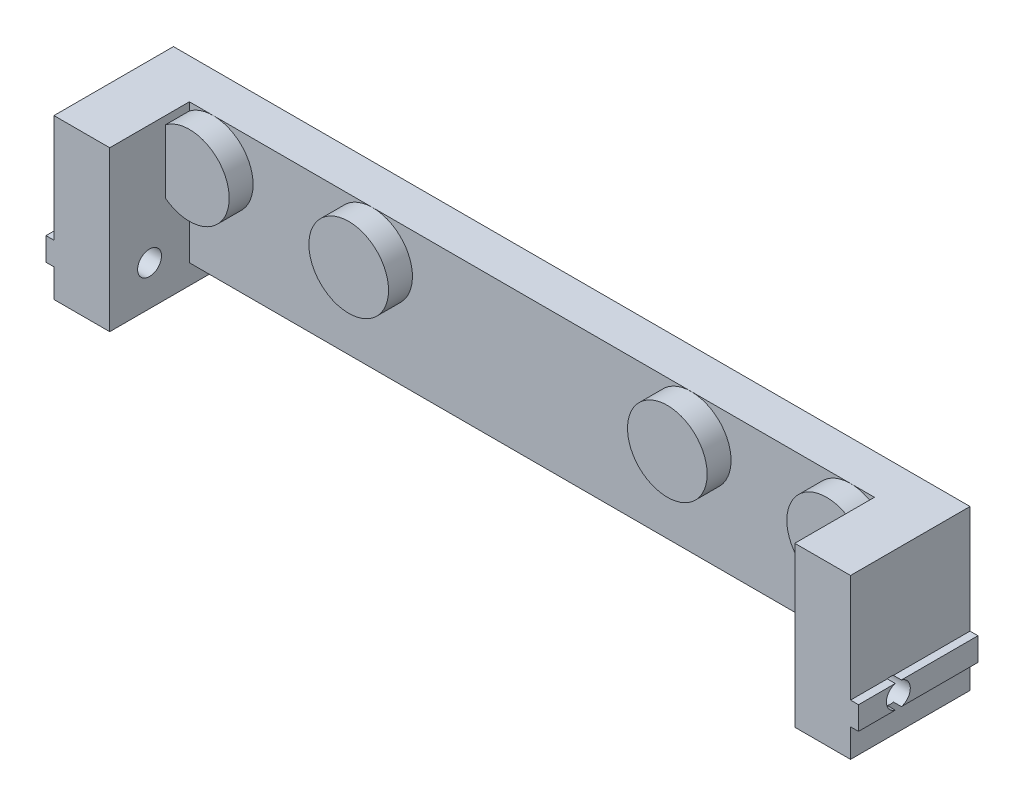
SolidWorks part; units mm, degrees
ref_plane "Front Plane" through (0, 0, 0) normal (0, 0, 1) x (1, 0, 0)
ref_plane "Top Plane" through (0, 0, 0) normal (0, 1, 0) x (1, 0, 0)
ref_plane "Right Plane" through (0, 0, 0) normal (1, 0, 0) x (0, 0, -1)
sketch "Sketch1" plane through (0, 0, 0) normal (0, 0, 1) x (1, 0, 0)
  line L0 (-50, 0) -> (50, 0)
  line L1 (-50, 0) -> (-50, 3.55)
  line L2 (-50, 3.55) -> (-51, 3.55)
  line L3 (-51, 3.55) -> (-51, 6.45)
  line L4 (-51, 6.45) -> (-50, 6.45)
  line L7 (-50, 6.45) -> (-50, 20)
  line L8 (-50, 20) -> (50, 20)
  line L9 (50, 20) -> (50, 6.45)
  line L12 (50, 6.45) -> (51, 6.45)
  line L13 (51, 6.45) -> (51, 3.55)
  line L14 (51, 3.55) -> (50, 3.55)
  line L15 (50, 3.55) -> (50, 0)
  point P24 (0, 0)
  dimension "D1" = 100
  dimension "D2" = 3.55
  dimension "D3" = 2.9
  dimension "D4" = 1
  dimension "D5" = 20
extrude "Main" add sketch "Sketch1" along normal blind 15
sketch "Sketch2" plane through (0, 0, 15) normal (0, 0, 1) x (1, 0, 0)
  line L0 (-50, 0) -> (50, 0) construction
  line L1 (-43, 0) -> (43, 0)
  line L2 (-43, 0) -> (-43, 20)
  line L3 (-43, 20) -> (43, 20)
  line L4 (43, 0) -> (43, 20)
  line L5 (-50, 3.55) -> (-50, 0) construction
  line L6 (50, 0) -> (50, 3.55) construction
  line L7 (50, 20) -> (-50, 20) construction
  point P10 (50, 1.775)
  dimension "D1" = 7
  dimension "D2" = 7
extrude "TopExtrusion" cut sketch "Sketch2" against normal blind 10
sketch "Sketch5" plane through (0, 0, 5) normal (0, 0, 1) x (1, 0, 0)
  line L0 (-43, 0) -> (43, 0) construction
  circle A0 centre (-40, 15) radius 5
  circle A1 centre (-20, 15) radius 5
  circle A2 centre (20, 15) radius 5
  circle A3 centre (40, 15) radius 5
  dimension "D1" = 10
  dimension "D2" = 15
  dimension "D3" = 40
  dimension "D4" = 40
  dimension "D5" = 20
  dimension "D6" = 20
extrude "ReinforcementHoles" add sketch "Sketch5" along normal blind 3
sketch "Sketch3" plane through (0, 0, 0) normal (0, 0, 1) x (1, 0, 0)
  line L0 (-43, 0) -> (43, 0) construction
  circle A0 centre (-40, 15) radius 3
  circle A1 centre (20, 15) radius 3
  dimension "D1" = 6
  dimension "D4" = 60
  dimension "D2" = 15
  dimension "D3" = 40
extrude "Holes" cut sketch "Sketch3" along normal blind 5
mirror "Mirror1" about plane through (0, 0, 0) normal (1, 0, 0) of "Holes"
sketch "Sketch4" plane through (51, 0, 0) normal (1, 0, 0) x (0, 0, -1)
  line L0 (-15, 0) -> (0, 0) construction
  line L1 (-15, 3.55) -> (-15, 6.45) construction
  circle A0 centre (-10, 5) radius 1.5
  dimension "D1" = 5
  dimension "D3" = 3
  dimension "D2" = 5
extrude "FixHoles" cut sketch "Sketch4" against normal through all
sketch "Sketch6" plane through (0, 0, 5) normal (0, 0, 1) x (1, 0, 0)
  line L0 (-43, 0) -> (43, 0) construction
  line L1 (43, 2.5) -> (-43, 2.5)
  line L2 (43, 2.5) -> (43, 0)
  line L3 (43, 0) -> (-43, 0)
  line L4 (-43, 2.5) -> (-43, 0)
  line L5 (-43, 20) -> (-43, 0) construction
  line L6 (-43, 11) -> (-43, 0) construction
  line L7 (43, 0) -> (43, 20) construction
  line L8 (43, 0) -> (43, 11) construction
  point P6 (-43, 0)
  point P11 (43, 0)
  dimension "D1" = 2.5
extrude "ForWindow" cut sketch "Sketch6" against normal through all
sketch "Sketch7" plane through (0, 2.5, 0) normal (0, -1, 0) x (-1, 0, 0)
  line L0 (-43, 0) -> (43, 0) construction
  line L1 (43, 0) -> (43, -5) construction
  line L2 (-43, 0) -> (-43, -5) construction
  circle A0 centre (36, -2.5) radius 1.25
  circle A1 centre (-36, -2.5) radius 1.25
  point P4 (0, 0)
  dimension "D1" = 2.5
  dimension "D2" = 2.5
  dimension "D3" = 7
  dimension "D4" = 7
extrude "Cut-Extrude2" cut sketch "Sketch7" against normal blind 10
